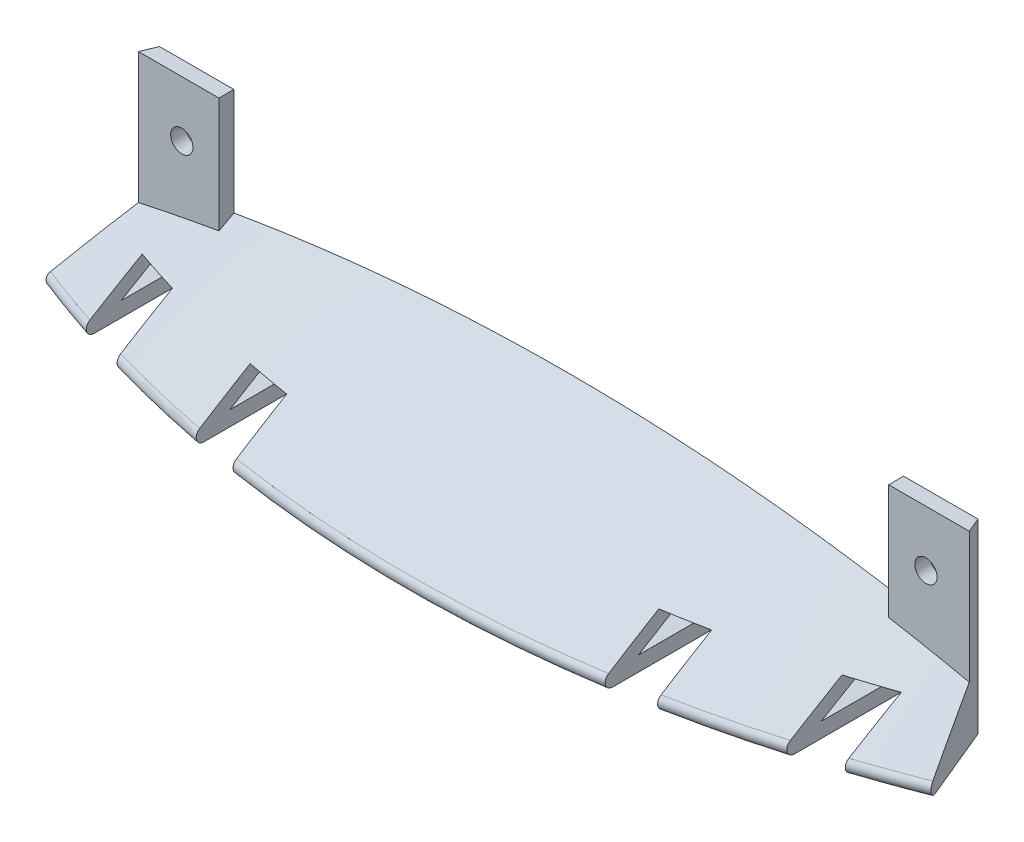
SolidWorks part; units mm, degrees
ref_plane "前视基准面" through (0, 0, 0) normal (0, 0, 1) x (1, 0, 0)
ref_plane "上视基准面" through (0, 0, 0) normal (0, 1, 0) x (1, 0, 0)
ref_plane "右视基准面" through (0, 0, 0) normal (1, 0, 0) x (0, 0, -1)
other "Configuration Table"
sketch "草图1" plane through (0, 0, 0) normal (0, 1, 0) x (1, 0, 0)
  line L0 (-57.4025, 138.5819) -> (57.4025, 138.5819) construction
  line L1 (57.4025, 138.5819) -> (138.5819, 57.4025) construction
  line L2 (138.5819, 57.4025) -> (138.5819, -57.4025) construction
  line L3 (138.5819, -57.4025) -> (57.4025, -138.5819) construction
  line L4 (57.4025, -138.5819) -> (-57.4025, -138.5819) construction
  line L5 (-57.4025, -138.5819) -> (-138.5819, -57.4025) construction
  line L6 (-138.5819, -57.4025) -> (-138.5819, 57.4025) construction
  line L7 (-138.5819, 57.4025) -> (-57.4025, 138.5819) construction
  line L8 (-138.5819, 0) -> (138.5819, 0) construction
  line L9 (-55, -140.5819) -> (55, -140.5819)
  line L10 (0, -138.5819) -> (0, -140.5819) construction
  line L11 (0, 0) -> (-58.2309, -140.5819) construction
  line L12 (-58.2309, -140.5819) -> (-68.3452, -165) construction
  line L13 (-65.1143, -165) -> (65.1143, -165)
  line L14 (65.1143, -165) -> (55, -140.5819) construction
  line L15 (0, -140.5819) -> (0, -165) construction
  line L16 (-55, -140.5819) -> (-65.1143, -165)
  line L17 (55, -140.5819) -> (65.1143, -165)
  line L18 (-58.2309, -140.5819) -> (-55, -140.5819) construction
  line L19 (-68.3452, -165) -> (-65.1143, -165) construction
  point P10 (0, 0)
  dimension "D1" = 45
  dimension "D2" = 300
  dimension "D3" = 2
  dimension "D4" = 165
  dimension "D5" = 110
extrude "凸台-拉伸1" add sketch "草图1" along normal blind 20
sketch "草图2" plane through (0, 0, 0) normal (1, 0, 0) x (0, 0, -1)
  line L0 (0, -250.5494) -> (0, 0) construction
  line L1 (0, -250.5494) -> (-165, 0) construction
  line L2 (0, 0) -> (0, 49.4506) construction
  line L3 (-165, 0) -> (-265, 0)
  line L4 (0, 49.4506) -> (0, 114.1423)
  arc A0 (-165, 0) -> (0, 49.4506) centre (0, -250.5494) cw
  arc A1 (-265, 0) -> (0, 114.1423) centre (0, -250.5494) cw
  dimension "D1" = 100
  dimension "D2" = 300
revolve "切除-旋转2" cut sketch "草图2" angle 360 about L2
sketch "草图3" plane through (0, 0, 140.5819) normal (0, 0, -1) x (-1, 0, 0)
  line L0 (0, 0) -> (0, 31.6848) construction
  line L1 (-55, 0) -> (-45, 0)
  line L2 (-55, 0) -> (-55, 25)
  line L3 (-55, 25) -> (-45, 25)
  line L4 (-45, 0) -> (-45, 25)
  line L5 (-55, 0) -> (55, 0) construction
  line L6 (-50, 0) -> (-50, 25) construction
  line L7 (50, 0) -> (50, 25) construction
  line L8 (45, 0) -> (45, 25)
  line L9 (55, 25) -> (45, 25)
  line L10 (55, 0) -> (55, 25)
  line L11 (55, 0) -> (45, 0)
  circle A0 centre (-50, 17.5) radius 1.5
  circle A1 centre (50, 17.5) radius 1.5
  dimension "D4" = 3
  dimension "D1" = 10
  dimension "D2" = 25
  dimension "D3" = 7.5
extrude "凸台-拉伸2" add sketch "草图3" against normal blind 2
sketch "草图4" plane through (55, 0, 0) normal (1, 0, 0) x (0, 0, -1)
  line L0 (-142.5819, 0) -> (-140.5819, 0)
  line L3 (-142.5819, 25) -> (-142.5819, 7.6083)
  line L4 (-140.5819, 8.7028) -> (-140.5819, 25)
  line L5 (-140.5819, 25) -> (-142.5819, 25)
  line L6 (-142.5819, 25) -> (-142.5819, 0)
  line L7 (-140.5819, 0) -> (-140.5819, 25)
  line L8 (-140.5819, 25) -> (-142.5819, 25)
  arc A1 (-140.5819, 8.7028) -> (-142.5819, 7.6083) centre (0, -250.5494) ccw
  dimension "D1" = 0
extrude "凸台-拉伸3" add sketch "草图4" along normal up to surface up to face at (56.7992, 2.9332, 144.9256)
sketch "草图5" plane through (-55, 0, 0) normal (-1, 0, 0) x (0, 0, 1)
  line L0 (140.5819, 0) -> (153.5575, 0) construction
  line L1 (140.5819, 0) -> (142.5819, 0)
  line L3 (140.5819, 25) -> (140.5819, 8.7028)
  line L4 (142.5819, 7.6083) -> (142.5819, 25)
  line L5 (142.5819, 25) -> (140.5819, 25)
  line L6 (140.5819, 25) -> (140.5819, 0)
  line L7 (142.5819, 0) -> (142.5819, 25)
  line L8 (142.5819, 25) -> (140.5819, 25)
  arc A1 (142.5819, 7.6083) -> (140.5819, 8.7028) centre (0, -250.5494) ccw
  dimension "D1" = 0
extrude "凸台-拉伸4" add sketch "草图5" along normal up to surface (0.8284 mm away) up to face at (-56.7992, 2.9332, 144.9256)
fillet "圆角3" radius 1 1 edges at (0, 0, 165)
shell "抽壳2" thickness 2 removed face at (0, 15.6371, 140.5819)
sketch "草图7" plane through (0, 0, 140.5819) normal (0, 0, -1) x (-1, 0, 0)
  line L1 (-31.003, 6) -> (-25.003, 6)
  line L2 (-31.003, 6) -> (-31.003, 0)
  line L3 (-31.003, 0) -> (-25.003, 0)
  line L4 (-25.003, 6) -> (-25.003, 0)
  line L5 (0, 0) -> (0, 12.2066) construction
  line L6 (31.003, 6) -> (31.003, 0)
  line L7 (31.003, 0) -> (25.003, 0)
  line L8 (25.003, 6) -> (25.003, 0)
  line L9 (31.003, 6) -> (25.003, 6)
  line L10 (-55, 0) -> (55, 0) construction
  line L11 (45.003, 6) -> (45.003, 0)
  line L12 (-51.003, 6) -> (-45.003, 6)
  line L13 (-51.003, 6) -> (-51.003, 0)
  line L14 (-51.003, 0) -> (-45.003, 0)
  line L15 (-45.003, 6) -> (-45.003, 0)
  line L16 (51.003, 6) -> (45.003, 6)
  line L17 (51.003, 6) -> (51.003, 0)
  line L18 (51.003, 0) -> (45.003, 0)
  arc A0 (52.8352, 6.8397) -> (-52.8352, 6.8397) centre (0, -250.5494) ccw construction
  dimension "D1" = 25.003
  dimension "D2" = 6
  dimension "D3" = 6
  dimension "D4" = 6
  dimension "D5" = 14
  dimension "D6" = 6
extrude "切除-拉伸2" cut sketch "草图7" against normal through all
